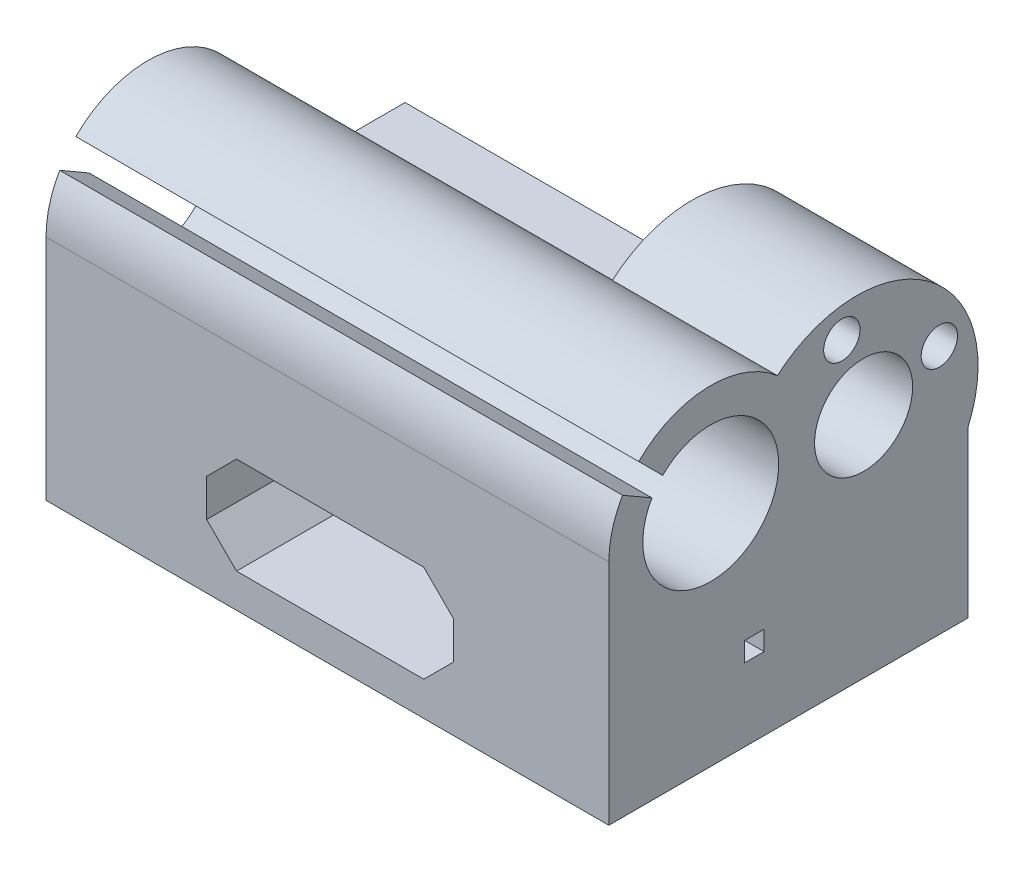
SolidWorks part; units mm, degrees
ref_plane "Front Plane" through (0, 0, 0) normal (0, 0, 1) x (1, 0, 0)
ref_plane "Top Plane" through (0, 0, 0) normal (0, 1, 0) x (1, 0, 0)
ref_plane "Right Plane" through (0, 0, 0) normal (1, 0, 0) x (0, 0, -1)
sketch "Sketch2" plane through (0, 0, 0) normal (0, 1, 0) x (1, 0, 0)
  line L1 (-29, -18.5) -> (29, -18.5)
  line L2 (-29, -18.5) -> (-29, 18.5)
  line L3 (-29, 18.5) -> (29, 18.5)
  line L4 (29, -18.5) -> (29, 18.5)
  line L5 (-29, -18.5) -> (29, 18.5) construction
  line L6 (-29, 18.5) -> (29, -18.5) construction
  point P0 (0, 0)
  dimension "D1" = 58
  dimension "D2" = 37
extrude "Boss-Extrude1" add sketch "Sketch2" along normal blind 17
sketch "Sketch3" plane through (29, 0, 0) normal (1, 0, 0) x (0, 0, -1)
  line L0 (-18.5, 0) -> (18.5, 0) construction
  line L1 (-18.5, 23.5) -> (-18.5, 17)
  line L2 (-18.5, 17) -> (-18.5, 0) construction
  line L5 (2.5, 23.5) -> (2.5, 17)
  line L6 (-18.5, 17) -> (18.5, 17) construction
  line L7 (-18.5, 17) -> (2.5, 17)
  arc A0 (2.5, 23.5) -> (-18.5, 23.5) centre (-8, 23.5) ccw
  dimension "D2" = 21
  dimension "D4" = 23.5
  dimension "D5" = 10.5
extrude "Boss-Extrude2" add sketch "Sketch3" against normal up to surface (58 mm away) up to face at (-29, 8.5, 0)
sketch "Sketch4" plane through (29, 0, 0) normal (1, 0, 0) x (0, 0, -1)
  line L1 (-18.5, 0) -> (18.5, 0) construction
  circle A0 centre (7.0436, 22) radius 12.5
  dimension "D1" = 25
  dimension "D2" = 22
extrude "Boss-Extrude3" add sketch "Sketch4" against normal blind 17
sketch "Sketch5" plane through (0, 0, -18.5) normal (0, 0, -1) x (-1, 0, 0)
  line L0 (-13, 6.57) -> (-13, 10.427)
  line L1 (-13, 10.427) -> (-9.93, 13.497)
  line L2 (-9.93, 13.497) -> (9.37, 13.497)
  line L3 (9.37, 13.497) -> (12.44, 10.427)
  line L4 (12.44, 10.427) -> (12.44, 6.57)
  line L5 (12.44, 6.57) -> (9.37, 3.5)
  line L6 (9.37, 3.5) -> (-9.93, 3.5)
  line L7 (-9.93, 3.5) -> (-13, 6.57)
  line L8 (-29, 0) -> (29, 0) construction
  line L9 (-29, 17) -> (-29, 0) construction
  dimension "D1" = 3.857
  dimension "D2" = 3.857
  dimension "D3" = 135
  dimension "D4" = 135
  dimension "D5" = 3.07
  dimension "D6" = 3.07
  dimension "D7" = 3.07
  dimension "D8" = 3.07
  dimension "D9" = 19.3
  dimension "D10" = 3.5
  dimension "D11" = 16
extrude "Cut-Extrude1" cut sketch "Sketch5" against normal through all
sketch "Sketch6" plane through (0, 0, -18.5) normal (0, 0, -1) x (-1, 0, 0)
  line L0 (-29, 0) -> (29, 0) construction
  line L1 (-29, 17) -> (-29, 0) construction
  circle A0 centre (-23, 8.5) radius 4.076
  circle A1 centre (22, 8.5) radius 4.076
  dimension "D5" = 8.152
  dimension "D6" = 8.152
  dimension "D1" = 8.5
  dimension "D2" = 8.5
  dimension "D3" = 6
  dimension "D4" = 51
extrude "Cut-Extrude2" cut sketch "Sketch6" against normal blind 23
sketch "Sketch7" plane through (29, 0, 0) normal (1, 0, 0) x (0, 0, -1)
  line L0 (-18.5, 23.5) -> (-18.5, 0) construction
  line L1 (-18.5, 0) -> (18.5, 0) construction
  circle A0 centre (-8, 23.5) radius 7
  circle A1 centre (7.7501, 23.5) radius 5.05
  dimension "D1" = 10.1
  dimension "D2" = 14
  dimension "D3" = 26.2501
  dimension "D4" = 23.5
extrude "Cut-Extrude3" cut sketch "Sketch7" against normal through all
sketch "Sketch8" plane through (29, 0, 0) normal (1, 0, 0) x (0, 0, -1)
  line L0 (7.7501, 23.5) -> (5.5097, 31.31) construction
  line L3 (7.7501, 23.5) -> (15.5601, 25.7405) construction
  line L4 (5.5097, 31.31) -> (6.0267, 29.5077) construction
  line L7 (15.5601, 25.7405) -> (13.7578, 25.2235) construction
  circle A1 centre (5.5097, 31.31) radius 1.875
  circle A2 centre (15.5601, 25.7405) radius 1.875
  dimension "D1" = 3.75
  dimension "D2" = 6.25
  dimension "D3" = 3.75
  dimension "D7" = 6.25
extrude "Cut-Extrude4" cut sketch "Sketch8" against normal through all
sketch "Sketch9" plane through (12, 0, 0) normal (-1, 0, 0) x (0, 0, 1)
  circle A0 centre (-5.5097, 31.31) radius 2.75
  circle A1 centre (-15.5601, 25.7405) radius 2.75
  dimension "D1" = 5.5
  dimension "D2" = 5.5
sketch "Sketch10" plane through (29, 0, 0) normal (1, 0, 0) x (0, 0, -1)
  line L0 (-8, 23.5) -> (-15.4246, 30.9246) construction
  line L1 (-8, 23.5) -> (-29.5432, 23.5) construction
  line L2 (-8, 23.5) -> (-17.0933, 28.75) construction
  line L3 (-12.9497, 28.4497) -> (-15.4246, 30.9246)
  line L4 (-17.0933, 28.75) -> (-14.0622, 27)
  arc A0 (-1.1397, 31.449) -> (-18.5, 23.5) centre (-8, 23.5) ccw construction
  arc A1 (-12.9497, 28.4497) -> (-14.0622, 27) centre (-8, 23.5) ccw
  arc A2 (-18.5, 23.5) -> (-17.0933, 28.75) centre (-8, 23.5) ccw
  circle A3 centre (-8, 23.5) radius 7 construction
  circle M9 centre (-8, 23.5) radius 7
  arc M13 (-1.1397, 31.449) -> (-18.5, 23.5) centre (-8, 23.5) ccw
  dimension "D1" = 15
  dimension "D2" = 30
extrude "Cut-Extrude5" cut sketch "Sketch10" against normal through all contours L4 L3 M13 M9 region at (29, 28.8823, 15.0143)
sketch "Sketch12" plane through (-29, 0, 0) normal (-1, 0, 0) x (0, 0, 1)
  line L0 (-18.5, 17) -> (-18.5, 0) construction
  line L1 (4.5, 7.5) -> (2.5, 7.5)
  line L2 (4.5, 7.5) -> (4.5, 9.5)
  line L3 (4.5, 9.5) -> (2.5, 9.5)
  line L4 (2.5, 7.5) -> (2.5, 9.5)
  line L5 (-18.5, 0) -> (18.5, 0) construction
  dimension "D1" = 23
  dimension "D2" = 2
  dimension "D3" = 2
  dimension "D4" = 7.5
extrude "Cut-Extrude6" cut sketch "Sketch12" against normal blind 8
mirror "Mirror1" about plane through (0, 0, 0) normal (1, 0, 0) of "Cut-Extrude6"
sketch "Sketch13" plane through (0, 0, 0) normal (0, -1, 0) x (1, 0, 0)
  line L0 (29, -18.5) -> (-29, -18.5) construction
  line L1 (29, 18.5) -> (29, -18.5) construction
  circle A0 centre (1, -11.5) radius 1.6587
  dimension "D1" = 3.3175
  dimension "D2" = 7
  dimension "D3" = 28
extrude "Cut-Extrude7" cut sketch "Sketch13" against normal through all
